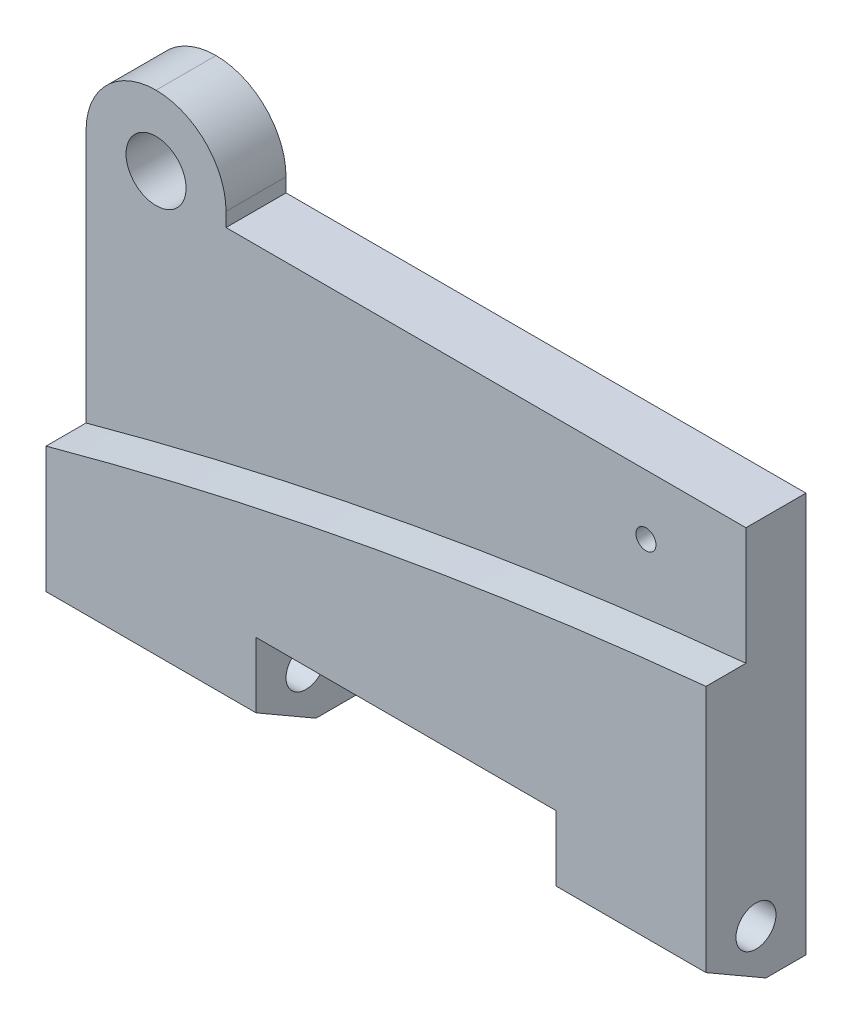
SolidWorks part; units mm, degrees
ref_plane "Plano frontal" through (0, 0, 0) normal (0, 0, 1) x (1, 0, 0)
ref_plane "Plano superior" through (0, 0, 0) normal (0, 1, 0) x (1, 0, 0)
ref_plane "Plano direito" through (0, 0, 0) normal (1, 0, 0) x (0, 0, -1)
sketch "Esboço1" plane through (0, 0, 0) normal (0, 0, 1) x (1, 0, 0)
  line L0 (9, -10) -> (16.5, -10)
  line L1 (-16.5, -10) -> (-6, -10)
  line L2 (-16.5, -10) -> (-16.5, 10)
  line L3 (-16.5, 10) -> (16.5, 10)
  line L4 (16.5, -10) -> (16.5, 10)
  line L5 (-16.5, -10) -> (16.5, 10) construction
  line L6 (-16.5, 10) -> (16.5, -10) construction
  line L8 (-6, -10) -> (-6, -5)
  line L9 (-6, -5) -> (9, -5)
  line L10 (9, -10) -> (9, -5)
  point P0 (0, 0)
  dimension "D1" = 20
  dimension "D2" = 33
  dimension "D3" = 5
  dimension "D4" = 15
  dimension "D5" = 7.5
extrude "Ressalto-extrusão1" add sketch "Esboço1" along normal blind 5
sketch "Esboço2" plane through (16.5, 0, 0) normal (1, 0, 0) x (0, 0, -1)
  line L0 (-5, -10) -> (0, -10) construction
  line L1 (0, -10) -> (0, 10) construction
  circle A0 centre (-2.5, -7.5) radius 1
  dimension "D1" = 2.5
  dimension "D2" = 2.5
  dimension "D3" = 2
extrude "Corte-extrusão1" cut sketch "Esboço2" against normal through all
sketch "Esboço3" plane through (0, 0, 5) normal (0, 0, 1) x (1, 0, 0)
  line L0 (35.7914, 7.2266) -> (35.7914, -392.7734) construction
  line L1 (-16.5, 10) -> (-16.5, -10) construction
  line L3 (-16.5, -1.9638) -> (-16.5, 10)
  line L4 (-16.5, 10) -> (16.5, 10)
  line L5 (16.5, 5.5234) -> (16.5, 10)
  line L6 (92.9681, -3.3703) -> (-21.3852, -3.3703) construction
  circle A0 centre (35.7914, -192.7734) radius 197.8452
  line M1 (16.5, -10) -> (16.5, 10)
  line M2 (16.5, 10) -> (-16.5, 10)
  line M3 (-16.5, 10) -> (-16.5, -10)
  dimension "D1" = 400
extrude "Corte-extrusão2" cut sketch "Esboço3" against normal blind 2 contours A0 M1 M2 M3 region at (-1.9836, 5.5974, 5)
sketch "Sketch1" plane through (0, 0, 0) normal (0, 0, -1) x (-1, 0, 0)
  circle A1 centre (-11.5, 7) radius 0.5
extrude "Cut-Extrude1" cut sketch "Sketch1" against normal through all
ref_plane "Plane1" through (-26.5, 0, 0) normal (-1, 0, 0) x (0, 0, 1)
sketch "Sketch2" plane through (0, 10, 0) normal (0, 1, 0) x (1, 0, 0)
  line L0 (16.5, 0) -> (-16.5, 0) construction
  line L1 (-16.5, -3) -> (-9.5, -3)
  line L2 (-16.5, -3) -> (-16.5, 0)
  line L3 (-16.5, 0) -> (-9.5, 0)
  line L4 (-9.5, -3) -> (-9.5, 0)
  dimension "D1" = 7
extrude "Boss-Extrude1" add sketch "Sketch2" along normal blind 4.2
sketch "Sketch3" plane through (0, 0, 0) normal (0, 0, -1) x (-1, 0, 0)
  line L0 (9.5, 14.2) -> (16.5, 14.2) construction
  circle A0 centre (13, 10.7) radius 1.5
  dimension "D1" = 3.5
extrude "Cut-Extrude2" cut sketch "Sketch3" against normal through all
fillet "Fillet2" radius 3.5 2 edges at (-9.5, 14.2, 1.5) (-16.5, 14.2, 1.5)
chamfer "Chamfer1" distance 3 angle 30 2 edges at (-11.25, -10, 5) (12.75, -10, 5) first distance on face at (-11.25, -10, 2.5) first distance on face at (12.75, -10, 2.5)
